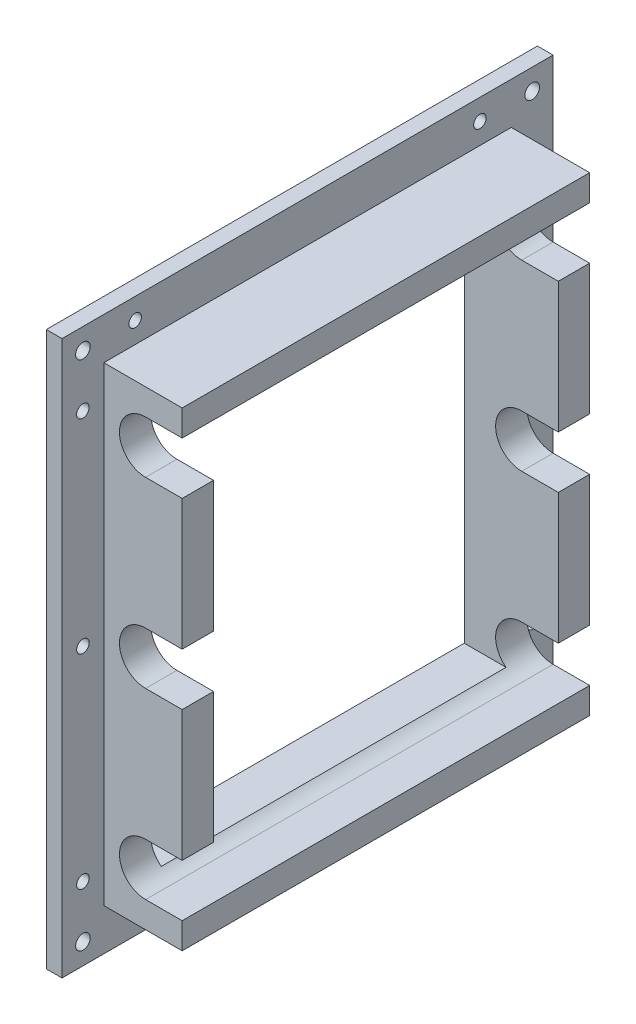
SolidWorks part; units mm, degrees
ref_plane "前视基准面" through (0, 0, 0) normal (0, 0, 1) x (1, 0, 0)
ref_plane "上视基准面" through (0, 0, 0) normal (0, 1, 0) x (1, 0, 0)
ref_plane "右视基准面" through (0, 0, 0) normal (1, 0, 0) x (0, 0, -1)
other "Configuration Table"
sketch "草图1" plane through (0, 0, 0) normal (1, 0, 0) x (0, 0, -1)
  line L0 (-235, 0) -> (0, 0) construction
  line L1 (-235, 265) -> (235, 265)
  line L2 (-235, 265) -> (-235, -265)
  line L3 (-235, -265) -> (235, -265)
  line L4 (235, 265) -> (235, -265)
  line L5 (-235, 265) -> (235, -265) construction
  line L6 (-235, -265) -> (235, 265) construction
  line L7 (-165, 195) -> (165, 195)
  line L8 (-165, 195) -> (-165, -195)
  line L9 (-165, -195) -> (165, -195)
  line L10 (165, 195) -> (165, -195)
  line L11 (-165, 195) -> (165, -195) construction
  line L12 (-165, -195) -> (165, 195) construction
  line L13 (0, 0) -> (0, 265) construction
  circle A0 centre (-215, 245) radius 7
  circle A1 centre (-165, 245) radius 6
  circle A2 centre (-215, 195) radius 6
  circle A3 centre (215, 245) radius 7
  circle A4 centre (165, 245) radius 6
  circle A5 centre (215, 195) radius 6
  circle A6 centre (-215, -195) radius 6
  circle A7 centre (-165, -245) radius 6
  circle A8 centre (-215, -245) radius 7
  circle A9 centre (165, -245) radius 6
  circle A10 centre (215, -245) radius 7
  circle A11 centre (215, -195) radius 6
  circle A12 centre (-215, 0) radius 6
  circle A13 centre (215, 0) radius 6
  point P0 (0, 0)
  point P6 (0, 0)
  point P20 (0, 0)
  dimension "D6" = 490
  dimension "D7" = 14
  dimension "D10" = 12
  dimension "D11" = 12
  dimension "D1" = 390
  dimension "D2" = 330
  dimension "D3" = 470
  dimension "D4" = 530
  dimension "D5" = 430
  dimension "D8" = 330
  dimension "D9" = 390
extrude "凸台-拉伸1" add sketch "草图1" along normal blind 15
sketch "草图2" plane through (15, 0, 0) normal (1, 0, 0) x (0, 0, -1)
  line L1 (-195, 225) -> (195, 225)
  line L2 (-195, 225) -> (-195, -225)
  line L3 (-195, -225) -> (195, -225)
  line L4 (195, 225) -> (195, -225)
  line L5 (-195, 225) -> (195, -225) construction
  line L6 (-195, -225) -> (195, 225) construction
  line L10 (165, 195) -> (-165, 195)
  line L11 (165, -195) -> (165, 195)
  line L12 (-165, -195) -> (165, -195)
  line L13 (-165, 195) -> (-165, -195)
  line L14 (165, 195) -> (-165, 195)
  line L15 (165, -195) -> (165, 195)
  line L16 (-165, -195) -> (165, -195)
  line L17 (-165, 195) -> (-165, -195)
  point P0 (0, 0)
  dimension "D1" = 390
  dimension "D2" = 450
  dimension "D3" = 0
extrude "凸台-拉伸2" add sketch "草图2" along normal blind 75
sketch "草图4" plane through (0, 0, 195) normal (0, 0, 1) x (1, 0, 0)
  line L0 (0, 0) -> (90, 0) construction
  line L1 (90, 225) -> (90, -225) construction
  line L2 (90, 25) -> (55, 25)
  line L3 (55, -25) -> (90, -25)
  line L4 (90, -25) -> (90, 25)
  line L5 (90, 200) -> (55, 200)
  line L6 (55, 150) -> (90, 150)
  line L7 (90, 150) -> (90, 200)
  line L8 (90, -150) -> (90, -200)
  line L9 (55, -150) -> (90, -150)
  line L10 (90, -200) -> (55, -200)
  arc A0 (55, 25) -> (55, -25) centre (55, 0) ccw
  arc A1 (55, 200) -> (55, 150) centre (55, 175) ccw
  arc A2 (55, -200) -> (55, -150) centre (55, -175) cw
  point P14 (0, 0)
  point P16 (90, 175)
  dimension "D1" = 25
  dimension "D2" = 35
  dimension "D3" = 350
  dimension "D4" = 35
extrude "切除-拉伸1" cut sketch "草图4" against normal through all
